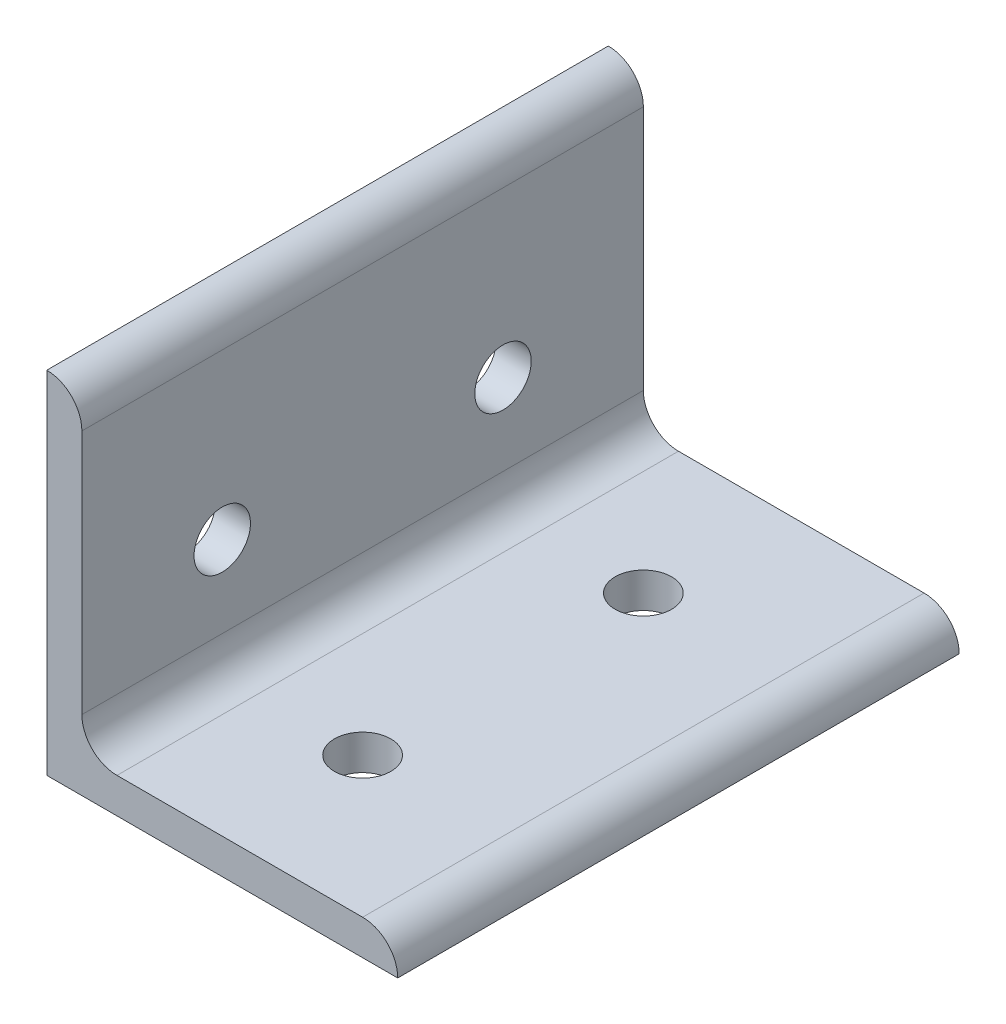
SolidWorks part; units mm, degrees
ref_plane "Front Plane" through (0, 0, 0) normal (0, 0, 1) x (1, 0, 0)
ref_plane "Top Plane" through (0, 0, 0) normal (0, 1, 0) x (1, 0, 0)
ref_plane "Right Plane" through (0, 0, 0) normal (1, 0, 0) x (0, 0, -1)
sketch "Sketch1" plane through (0, 0, 0) normal (0, 0, 1) x (1, 0, 0)
  line L0 (0, 0) -> (0, 31.75)
  line L1 (0, 0) -> (31.75, 0)
  line L2 (0, 31.75) -> (3.175, 31.75)
  line L3 (3.175, 31.75) -> (3.175, 3.175)
  line L4 (3.175, 3.175) -> (31.75, 3.175)
  line L5 (31.75, 3.175) -> (31.75, 0)
  dimension "D1" = 3.175
  dimension "D2" = 3.175
  dimension "D3" = 31.75
  dimension "D4" = 31.75
extrude "Boss-Extrude1" add sketch "Sketch1" along normal mid plane 50.8
sketch "Sketch2" plane through (0, 0, 0) normal (-1, 0, 0) x (0, 0, 1)
  line L0 (25.4, 0) -> (-25.4, 0) construction
  line L1 (25.4, 3.175) -> (25.4, 31.75) construction
  circle A0 centre (-12.7, 13.716) radius 2.5527
  circle A1 centre (12.7, 13.716) radius 2.5527
  dimension "D4" = 5.1054
  dimension "D5" = 5.1054
  dimension "D1" = 13.716
  dimension "D2" = 13.716
  dimension "D3" = 25.4
  dimension "D6" = 12.7
extrude "Cut-Extrude1" cut sketch "Sketch2" against normal through all
sketch "Sketch3" plane through (0, 0, 0) normal (0, -1, 0) x (1, 0, 0)
  line L0 (0, 25.4) -> (0, -25.4) construction
  line L1 (0, 25.4) -> (31.75, 25.4) construction
  circle A0 centre (15.875, 12.7) radius 2.5527
  circle A1 centre (15.875, -12.7) radius 2.5527
  dimension "D1" = 5.1054
  dimension "D2" = 5.1054
  dimension "D3" = 25.4
  dimension "D4" = 15.875
  dimension "D5" = 12.7
extrude "Cut-Extrude2" cut sketch "Sketch3" against normal through all
fillet "Fillet1" radius 3.175 3 edges at (3.175, 31.75, 0) (31.75, 3.175, 0) (3.175, 3.175, 0)
